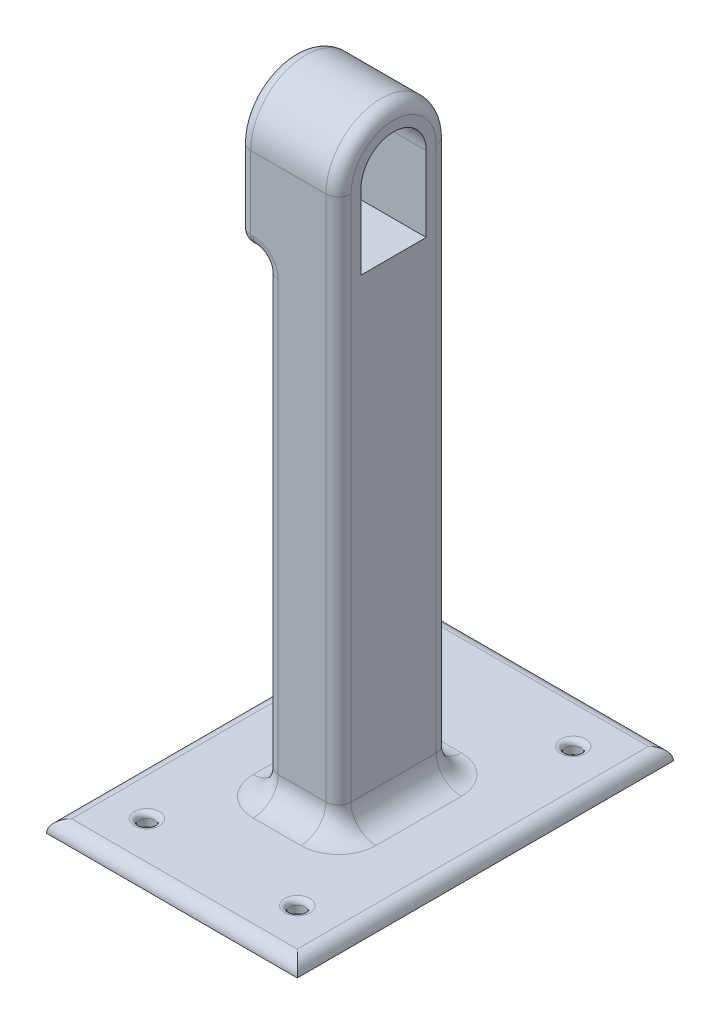
SolidWorks part; units mm, degrees
ref_plane "Front Plane" through (0, 0, 0) normal (0, 0, 1) x (1, 0, 0)
ref_plane "Top Plane" through (0, 0, 0) normal (0, 1, 0) x (1, 0, 0)
ref_plane "Right Plane" through (0, 0, 0) normal (1, 0, 0) x (0, 0, -1)
sketch "Sketch1" plane through (0, 0, 0) normal (0, 1, 0) x (1, 0, 0)
  line L0 (50, 0) -> (50, -158.6751) construction
  line L1 (0, 0) -> (100, 0)
  line L2 (0, 0) -> (0, -150)
  line L3 (0, -150) -> (100, -150)
  line L4 (100, 0) -> (100, -150)
  line L5 (0, -75) -> (100, -75) construction
  circle A0 centre (20, -20) radius 3
  circle A1 centre (80, -20) radius 3
  circle A2 centre (80, -130) radius 3
  circle A3 centre (20, -130) radius 3
  dimension "D3" = 6
  dimension "D1" = 150
  dimension "D2" = 100
  dimension "D4" = 20
  dimension "D5" = 20
extrude "bottom" add sketch "Sketch1" along normal blind 5
sketch "Sketch2" plane through (0, 5, 0) normal (0, 1, 0) x (1, 0, 0)
  line L0 (35.9591, -54.5588) -> (35.9591, -98.5588)
  line L1 (39.9591, -58.5588) -> (60.9591, -58.5588)
  line L2 (39.9591, -58.5588) -> (39.9591, -94.5588)
  line L3 (39.9591, -94.5588) -> (60.9591, -94.5588)
  line L4 (60.9591, -58.5588) -> (60.9591, -94.5588)
  line L5 (35.9591, -98.5588) -> (64.9591, -98.5588)
  line L6 (64.9591, -54.5588) -> (64.9591, -98.5588)
  line L7 (35.9591, -54.5588) -> (64.9591, -54.5588)
  dimension "D1" = 36
  dimension "D2" = 21
  dimension "D3" = 4
extrude "Boss-Extrude2" add sketch "Sketch2" along normal blind 190 contours L4 L1 L2 L3 | L0 L5 L6 L7 region at (50.4591, 5, 76.5588)
sketch "Sketch3" plane through (64.9591, 0, 0) normal (1, 0, 0) x (0, 0, -1)
  line L0 (-98.5588, 195) -> (-98.5588, 225)
  line L1 (-54.5588, 225) -> (-54.5588, 195)
  line L2 (-54.5588, 195) -> (-98.5588, 195)
  arc A0 (-98.5588, 225) -> (-54.5588, 225) centre (-76.5588, 225) cw
  dimension "D1" = 30
extrude "Boss-Extrude3" add sketch "Sketch3" against normal blind 40
sketch "Sketch4" plane through (64.9591, 0, 0) normal (1, 0, 0) x (0, 0, -1)
  line L0 (-89.5588, 195) -> (-89.5588, 225)
  line L1 (-63.5588, 225) -> (-63.5588, 195)
  line L2 (-63.5588, 195) -> (-89.5588, 195)
  line L5 (-150, 5) -> (0, 5) construction
  line L6 (-98.5588, 225) -> (-98.5588, 5) construction
  arc A0 (-89.5588, 225) -> (-63.5588, 225) centre (-76.5588, 225) cw
  dimension "D5" = 13
  dimension "D1" = 190
  dimension "D2" = 26
  dimension "D3" = 9
  dimension "D4" = 30
extrude "Cut-Extrude1" cut sketch "Sketch4" against normal blind 35
sketch "Sketch5" plane through (0, 195, 0) normal (0, -1, 0) x (1, 0, 0)
  line L1 (24.9591, 98.5588) -> (64.9591, 98.5588)
  line L2 (24.9591, 98.5588) -> (24.9591, 54.5588)
  line L3 (24.9591, 54.5588) -> (64.9591, 54.5588)
  line L4 (64.9591, 98.5588) -> (64.9591, 54.5588)
  dimension "D1" = 40
  dimension "D2" = 44
extrude "Boss-Extrude4" add sketch "Sketch5" along normal blind 4
fillet "Fillet1" radius 5 4 edges at (24.9591, 247, 76.5588) (24.9591, 208, 98.5588) (24.9591, 191, 76.5588) (24.9591, 208, 54.5588)
fillet "Fillet3" radius 5 7 edges at (26.4236, 192.4645, 97.0943) (26.4236, 192.4645, 56.0233) (32.9591, 191, 98.5588) (32.9591, 191, 54.5588) (35.9591, 191, 76.5588) (35.9591, 98, 54.5588) (35.9591, 98, 98.5588)
fillet "Fillet4" radius 5 3 edges at (64.9591, 115, 98.5588) (64.9591, 247, 76.5588) (64.9591, 115, 54.5588)
fillet "Fillet5" radius 10 8 edges at (37.4236, 5, 97.0943) (35.9591, 5, 76.5588) (37.4236, 5, 56.0233) (50.4591, 5, 54.5588) (63.4946, 5, 56.0233) (64.9591, 5, 76.5588) (63.4946, 5, 97.0943) (50.4591, 5, 98.5588)
fillet "Fillet6" radius 5 4 edges at (100, 5, 75) (50, 5, 0) (0, 5, 75) (50, 5, 150)
fillet "Fillet7" radius 2 4 edges at (80, 5, 133) (20, 5, 127) (80, 5, 17) (20, 5, 23)
